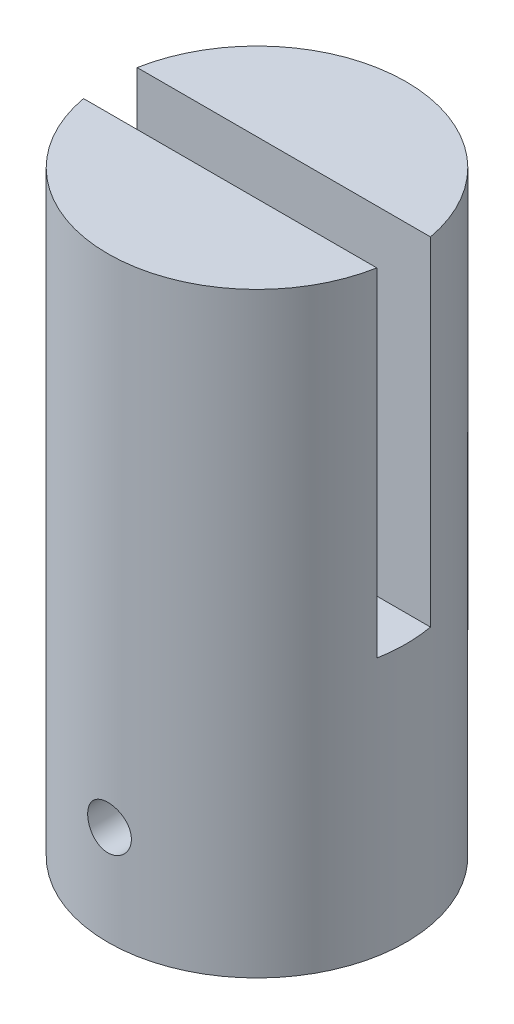
SolidWorks part; units mm, degrees
ref_plane "Front Plane" through (0, 0, 0) normal (0, 0, 1) x (1, 0, 0)
ref_plane "Top Plane" through (0, 0, 0) normal (0, 1, 0) x (1, 0, 0)
ref_plane "Right Plane" through (0, 0, 0) normal (1, 0, 0) x (0, 0, -1)
sketch "Sketch1" plane through (0, 0, 0) normal (0, 1, 0) x (1, 0, 0)
  circle A0 centre (0, 0) radius 2.5
  circle A1 centre (0, 0) radius 4
  circle A2 centre (0, 0) radius 7.5
  dimension "D1" = 5
  dimension "D2" = 8
  dimension "D3" = 15
extrude "Boss-Extrude1" add sketch "Sketch1" against normal blind 10 contours A1 A0 | A2 A1 region at (-3.8869, 0, 0) region at (-7.2879, 0, 0)
extrude "Boss-Extrude2" add sketch "Sketch1<3>" along normal blind 20 contours A2 A1 | A1 A0 | A0 region at (0, 0, 0) region at (-3.8869, 0, 0) region at (-7.2879, 0, 0)
sketch "Sketch1<3>" plane through (0, 0, 0) normal (0, 1, 0) x (1, 0, 0) same geometry as "Sketch1"
sketch "Sketch2" plane through (0, 20, 0) normal (0, 1, 0) x (1, 0, 0)
  line L0 (-7.3775, 1.35) -> (7.3775, 1.35)
  line L1 (-7.3775, -1.35) -> (7.3775, -1.35)
  circle A0 centre (0, 0) radius 7.5 construction
  arc A1 (-7.3775, 1.35) -> (-7.3775, -1.35) centre (0, 0) ccw
  arc A2 (7.3775, -1.35) -> (7.3775, 1.35) centre (0, 0) ccw
  dimension "D1" = 2.7
  dimension "D2" = 1.35
extrude "Cut-Extrude1" cut sketch "Sketch2" against normal blind 17
sketch "Sketch3" plane through (0, 0, 0) normal (0, 0, 1) x (1, 0, 0)
  circle A0 centre (0, -5) radius 1.1
  dimension "D1" = 2.2
extrude "Cut-Extrude2" cut sketch "Sketch3" against normal through all both and the other way through all
